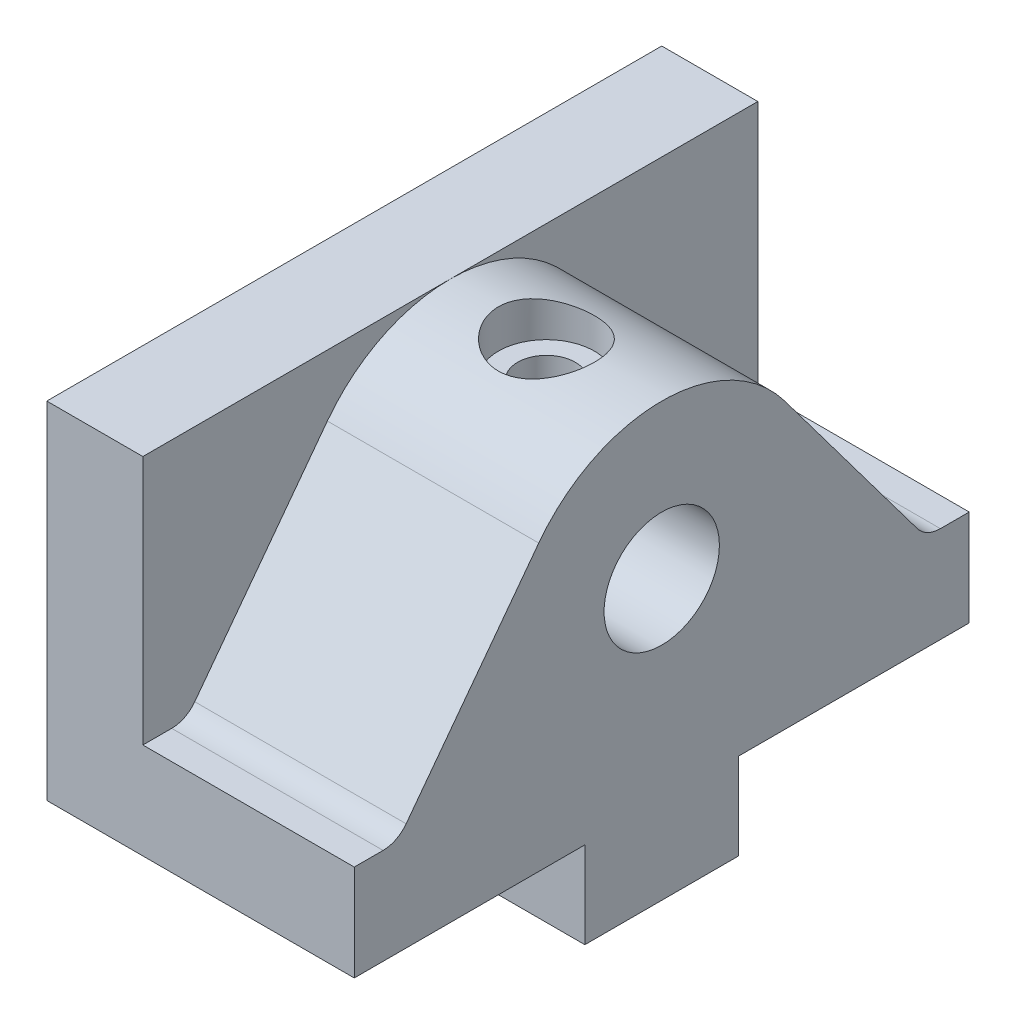
SolidWorks part; units mm, degrees
material "AISI 1020"
ref_plane "Front Plane" through (0, 0, 0) normal (0, 0, 1) x (1, 0, 0)
ref_plane "Top Plane" through (0, 0, 0) normal (0, 1, 0) x (1, 0, 0)
ref_plane "Right Plane" through (0, 0, 0) normal (1, 0, 0) x (0, 0, -1)
sketch "Sketch1" plane through (0, 0, 0) normal (1, 0, 0) x (0, 0, -1)
  line L0 (0, 0) -> (0, 40.8568) construction
  line L1 (-32, 45) -> (32, 45)
  line L2 (32, 45) -> (32, 9)
  line L3 (32, 9) -> (8, 9)
  line L4 (8, 9) -> (8, 0)
  line L5 (8, 0) -> (-8, 0)
  line L6 (-8, 0) -> (-8, 9)
  line L7 (-8, 9) -> (-32, 9)
  line L8 (-32, 9) -> (-32, 45)
  dimension "D1" = 16
  dimension "D2" = 64
  dimension "D3" = 9
  dimension "D4" = 36
extrude "Boss-Extrude1" add sketch "Sketch1" along normal blind 10 contours L2 L3 L4 L5 L6 L7 L8 L1
sketch "Sketch2" plane through (10, 0, 0) normal (1, 0, 0) x (0, 0, -1)
  line L0 (-8, 9) -> (-32, 9) construction
  line L1 (-8, 0) -> (-8, 9) construction
  line L2 (8, 0) -> (-8, 0) construction
  line L3 (8, 9) -> (8, 0) construction
  line L4 (32, 9) -> (8, 9) construction
  line L5 (32, 45) -> (32, 9) construction
  line L6 (-32, 45) -> (32, 45) construction
  line L7 (-32, 9) -> (-32, 45) construction
  line L8 (-8, 9) -> (-32, 9)
  line L9 (-8, 0) -> (-8, 9)
  line L10 (8, 0) -> (-8, 0)
  line L11 (8, 9) -> (8, 0)
  line L12 (32, 9) -> (8, 9)
  line L13 (32, 45) -> (32, 9)
  line L14 (-32, 45) -> (32, 45)
  line L15 (-32, 9) -> (-32, 45)
  line L16 (-32, 19) -> (-27.5, 19)
  line L17 (-27.5, 19) -> (-12.8, 38.6)
  line L18 (12.8, 38.6) -> (27.5, 19)
  line L19 (27.5, 19) -> (32, 19)
  line L20 (0, 0) -> (0, 45) construction
  arc A0 (-12.8, 38.6) -> (12.8, 38.6) centre (0, 29) cw
  line M10 (-32, 9) -> (-8, 9)
  line M11 (-8, 9) -> (-8, 0)
  line M12 (-8, 0) -> (8, 0)
  line M13 (8, 0) -> (8, 9)
  line M14 (8, 9) -> (32, 9)
  line M15 (32, 9) -> (32, 45)
  dimension "D3" = 16
  dimension "D1" = 10
  dimension "D2" = 55
extrude "Boss-Extrude2" add sketch "Sketch2" along normal blind 22 contours L20 L10 L19 L18 A0 M13 M14 M15 | L20 A0 L17 L16 L15 M12 M10 M11 region at (10, 21.4016, 11.665) region at (10, 21.4016, -11.665)
sketch "Sketch3" plane through (32, 0, 0) normal (1, 0, 0) x (0, 0, -1)
  circle A0 centre (0, 29) radius 6
  arc A1 (12.8, 38.6) -> (-12.8, 38.6) centre (0, 29) ccw construction
  dimension "D1" = 12
extrude "Cut-Extrude1" cut sketch "Sketch3" against normal blind 24
sketch "Sketch4" plane through (0, 45, 0) normal (0, 1, 0) x (1, 0, 0)
  point P0 (20, 0)
  dimension "D1" = 20
hole_wizard "CBORE for M5 Hex Head Bolt1" positions "3DSketch1" profile "Sketch5" counterbore size "M5" standard "ANSI Metric" end condition up to next
sketch3d "3DSketch1"
  point P0 (20, 45, 0)
sketch "Sketch5" plane through (20, 45, 0) normal (1, 0, 0) x (0, 0, 1)
  line L0 (0, 0) -> (0, 10)
  line L1 (0, 10) -> (3, 10)
  line L3 (3, 10) -> (3, 4)
  line L4 (3, 4) -> (5, 4)
  line L5 (5, 4) -> (5, 0)
  line L7 (5, 0) -> (0, 0)
  line L11 (0, -6.35) -> (0, 107.95) construction
  dimension "Thru Hole Dia." = 6
  dimension "Thru Hole Depth" = 10
  dimension "C'Bore Dia." = 10
  dimension "C'Bore Depth" = 4
hole_wizard "Tap Drill for M2.2 Helicoil1" positions "Sketch6" profile "Sketch7" hole size "M2.2x0.45" standard "ANSI Metric"
sketch "Sketch6" plane through (0, 0, 0) normal (0, -1, 0) x (-1, 0, 0)
  line L0 (-32, -8) -> (-32, 8) construction
  point P0 (-24, 0)
  dimension "D1" = 8
sketch "Sketch7" plane through (24, 0, 0) normal (1, 0, 0) x (0, 0, -1)
  line L0 (0, 0) -> (0, 16.664)
  line L1 (0, 16.664) -> (1.15, 16)
  line L2 (1.15, 16) -> (1.15, 0)
  line L5 (1.15, 0) -> (0, 0)
  line L10 (0, 16.664) -> (-1.15, 16) construction
  line L11 (0, -6.35) -> (0, 107.95) construction
  dimension "Hole Dia." = 2.3
  dimension "Hole Depth" = 16
  dimension "Drill Angle" = 120
pattern_linear "LPattern1" count 2 spacing 16 along (-1, 0, 0) of "Tap Drill for M2.2 Helicoil1"
fillet "Fillet1" radius 3 1 edges at (21, 19, 27.5)
fillet "Fillet2" radius 3 1 edges at (21, 19, -27.5)
